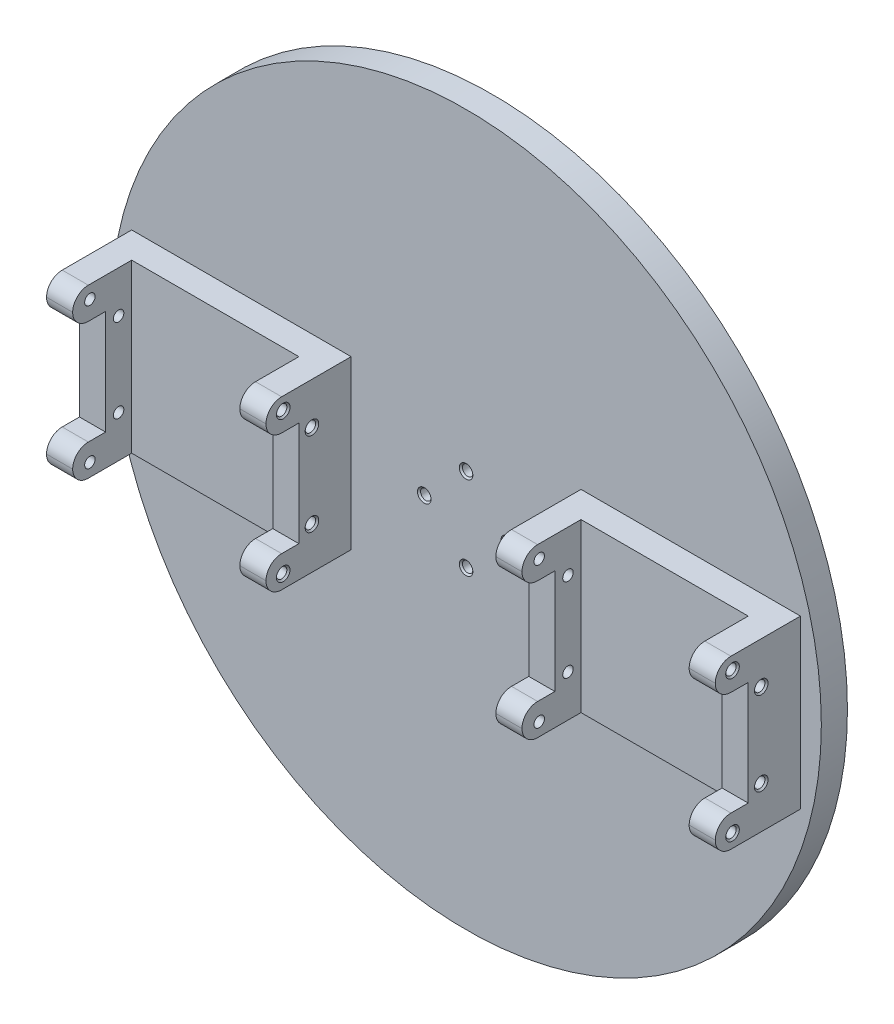
SolidWorks part; units mm, degrees
material "ABS"
ref_plane "Ön Düzlem" through (0, 0, 0) normal (0, 0, 1) x (1, 0, 0)
ref_plane "Üst Düzlem" through (0, 0, 0) normal (0, 1, 0) x (1, 0, 0)
ref_plane "Sağ Düzlem" through (0, 0, 0) normal (1, 0, 0) x (0, 0, -1)
sketch "Çizim1" plane through (0, 0, 0) normal (0, 0, 1) x (1, 0, 0)
  circle A0 centre (0, 0) radius 68
  dimension "D1" = 136
extrude "Yükseklik-Ekstrüzyon1" add sketch "Çizim1" along normal blind 5
sketch "Çizim2" plane through (0, 0, 5) normal (0, 0, 1) x (1, 0, 0)
  line L1 (-64, 16) -> (-22, 16)
  line L2 (-64, 16) -> (-64, -16)
  line L3 (-64, -16) -> (-22, -16)
  line L4 (-22, 16) -> (-22, -16)
  line L5 (-64, 16) -> (-22, -16) construction
  line L6 (-64, -16) -> (-22, 16) construction
  line L7 (22, 16) -> (64, 16)
  line L8 (22, 16) -> (22, -16)
  line L9 (22, -16) -> (64, -16)
  line L10 (64, 16) -> (64, -16)
  line L11 (22, 16) -> (64, -16) construction
  line L12 (22, -16) -> (64, 16) construction
  point P0 (-43, 0)
  point P5 (43, 0)
  dimension "D1" = 44
  dimension "D2" = 42
  dimension "D3" = 42
  dimension "D4" = 22
  dimension "D5" = 32
  dimension "D6" = 32
extrude "Yükseklik-Ekstrüzyon2" add sketch "Çizim2" along normal blind 16.3
sketch "Çizim3" plane through (0, 0, 21.3) normal (0, 0, 1) x (1, 0, 0)
  line L0 (-64, -16) -> (-22, -16) construction
  line L1 (-59, 16) -> (-27, 16)
  line L2 (-59, 16) -> (-59, -16)
  line L3 (-59, -16) -> (-27, -16)
  line L4 (-27, 16) -> (-27, -16)
  line L5 (-59, 16) -> (-27, -16) construction
  line L6 (-59, -16) -> (-27, 16) construction
  line L7 (22, -16) -> (64, -16) construction
  line L8 (27, 16) -> (59, 16)
  line L9 (27, 16) -> (27, -16)
  line L10 (27, -16) -> (59, -16)
  line L11 (59, 16) -> (59, -16)
  line L12 (27, 16) -> (59, -16) construction
  line L13 (27, -16) -> (59, 16) construction
  line L14 (-22, -16) -> (-22, 16) construction
  line L16 (64, -16) -> (64, 16) construction
  point P0 (-43, 0)
  point P7 (43, 0)
  dimension "D1" = 32
  dimension "D2" = 32
  dimension "D3" = 5
  dimension "D4" = 32
  dimension "D5" = 5
  dimension "D6" = 32
extrude "Kes-Ekstrüzyon1" cut sketch "Çizim3" against normal blind 11.3
ref_plane "Düzlem1" through (43, 0, 0) normal (1, 0, 0) x (0, 0, -1)
ref_plane "Düzlem2" through (0, 0, 0) normal (1, 0, 0) x (0, 0, -1)
sketch "Birinci Servo Bağlantı Noktaları" plane through (0, 0, 5) normal (0, 0, 1) x (1, 0, 0)
  circle A0 centre (0, 0) radius 11
  circle A1 centre (0, 0) radius 8
  point P4 (0, 8)
  point P5 (-8, 0)
  point P6 (0, -8)
  point P7 (8, 0)
  dimension "D1" = 22
  dimension "D2" = 16
hole_wizard "M2 Düz Başlı Makine Vidası İçin Havşa2" positions "3B Çizim2" profile "Çizim8" countersink size "M2" standard "ANSI Metrik" end condition up to next
sketch3d "3B Çizim2"
  point P0 (0, 8, 5)
  point P3 (8, 0, 5)
  point P6 (0, -8, 5)
  point P9 (-8, 0, 5)
sketch "Çizim8" plane through (0, 8, 5) normal (1, 0, 0) x (0, -1, 0)
  line L0 (0, 0) -> (0, 5)
  line L1 (0, 5) -> (1, 5)
  line L2 (1, 5) -> (1, 0.3)
  line L3 (1, 0.3) -> (1.3, 0)
  line L5 (1.3, 0) -> (0, 0)
  line L6 (-1, 0.3) -> (-1.3, 0) construction
  line L11 (0, -6.35) -> (0, 107.95) construction
  dimension "Thru Hole Dia." = 2
  dimension "Thru Hole Depth" = 5
  dimension "Near C'Sink Dia." = 2.6
  dimension "Near C'Sink Angle" = 90
sketch "Çizim9" plane through (64, 0, 0) normal (1, 0, 0) x (0, 0, -1)
  line L0 (-21.3, -16) -> (-21.3, 16) construction
  line L1 (-21.3, 10) -> (-15, 10)
  line L2 (-21.3, 10) -> (-21.3, -10)
  line L3 (-21.3, -10) -> (-15, -10)
  line L4 (-15, 10) -> (-15, -10)
  line L5 (-21.3, -16) -> (-5, -16) construction
  line L6 (-21.3, 16) -> (-5, 16) construction
  point P10 (-18, 13.5)
  point P11 (-12.5, 8)
  point P12 (-12.5, -8)
  point P13 (-18, -13.5)
  dimension "D1" = 6.3
  dimension "D2" = 6
  dimension "D3" = 6
  dimension "D4" = 2.5
  dimension "D5" = 3.3
  dimension "D6" = 2.5
  dimension "D7" = 2.5
  dimension "D8" = 8
  dimension "D9" = 8
extrude "Kes-Ekstrüzyon2" cut sketch "Çizim9" against normal through all
fillet "Radyus1" radius 3 16 edges at (-61.5, 10, 21.3) (-61.5, 16, 21.3) (61.5, -16, 21.3) (61.5, -10, 21.3) (24.5, -16, 21.3) (24.5, -10, 21.3) (61.5, 10, 21.3) (24.5, 10, 21.3) (24.5, 16, 21.3) (61.5, 16, 21.3) (-24.5, 10, 21.3) (-24.5, 16, 21.3) (-24.5, -16, 21.3) (-24.5, -10, 21.3) (-61.5, -16, 21.3) (-61.5, -10, 21.3)
hole_wizard "M2 Düz Başlı Makine Vidası İçin Havşa3" positions "3B Çizim3" profile "Çizim11" countersink size "M2" standard "ANSI Metrik"
sketch3d "3B Çizim3"
  point P0 (64, 13.5, 18)
  point P3 (64, 8, 12.5)
  point P6 (64, -8, 12.5)
  point P9 (64, -13.5, 18)
sketch "Çizim11" plane through (64, 13.5, 18) normal (0, 1, 0) x (0, 0, -1)
  line L0 (0, 0) -> (0, 5)
  line L1 (0, 5) -> (1, 5)
  line L2 (1, 5) -> (1, 0.3)
  line L3 (1, 0.3) -> (1.3, 0)
  line L5 (1.3, 0) -> (0, 0)
  line L6 (-1, 0.3) -> (-1.3, 0) construction
  line L10 (0, 5) -> (-1, 5) construction
  line L11 (0, -6.35) -> (0, 107.95) construction
  dimension "Hole Dia." = 2
  dimension "Hole Depth" = 5
  dimension "Near C'Sink Dia." = 2.6
  dimension "Near C'Sink Angle" = 90
  dimension "Drill Angle" = 180
mirror "Aynalama1" about plane through (43, 0, 0) normal (1, 0, 0) of "M2 Düz Başlı Makine Vidası İçin Havşa3"
mirror "Aynalama2" about plane through (0, 0, 0) normal (1, 0, 0) of "Aynalama1"
